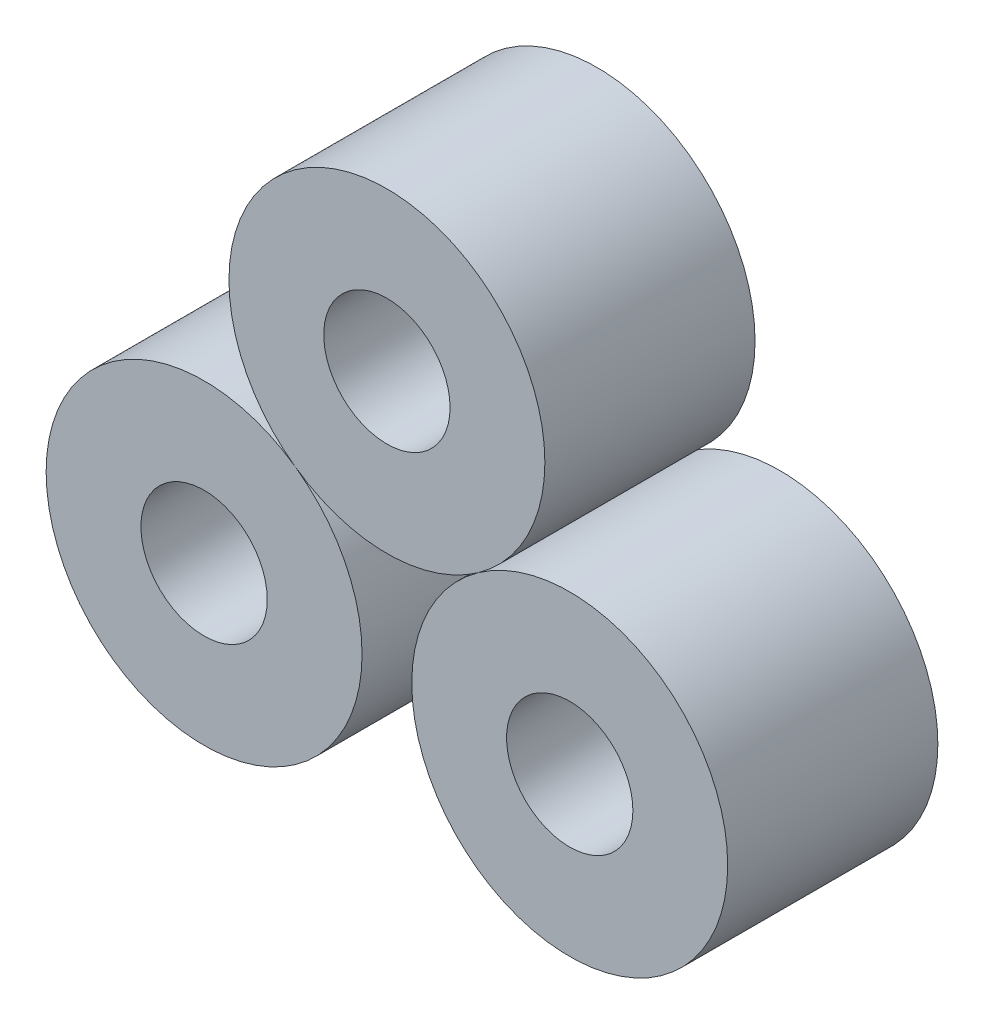
SolidWorks part; units mm, degrees
ref_plane "Płaszczyzna przednia" through (0, 0, 0) normal (0, 0, 1) x (1, 0, 0)
ref_plane "Płaszczyzna górna" through (0, 0, 0) normal (0, 1, 0) x (1, 0, 0)
ref_plane "Płaszczyzna prawa" through (0, 0, 0) normal (1, 0, 0) x (0, 0, -1)
sketch "Szkic1" plane through (0, 0, 0) normal (0, 0, 1) x (1, 0, 0)
  line L0 (0, 0) -> (2206, 0) construction
  circle A0 centre (0, 0) radius 381
  circle A1 centre (0, 0) radius 953
  circle A2 centre (2206, 0) radius 953
  circle A3 centre (2206, 0) radius 381
  circle A4 centre (3309, 1554.4218) radius 953 [skipped]
  circle A5 centre (3309, 1554.4218) radius 381 [skipped]
  circle A6 centre (1103, 1554.4218) radius 953
  circle A7 centre (1103, 1554.4218) radius 381
  dimension "D1" = 762
  dimension "D2" = 1906
  dimension "D5" = 2206
  dimension "D3" = 2
  dimension "D4" = 2
extrude "Dodanie-wyciągnięcie1" add sketch "Szkic1" along normal blind 1268 contours A2 | A1 | A3 | A0 | A6 | A7
ref_axis "Oś1" through (0, 0, 1268) along (0, 0, -1)
ref_axis "Oś2" through (2206, 0, 1268) along (0, 0, -1)
ref_axis "Oś3" through (1103, 1554.4218, 1268) along (0, 0, -1)
